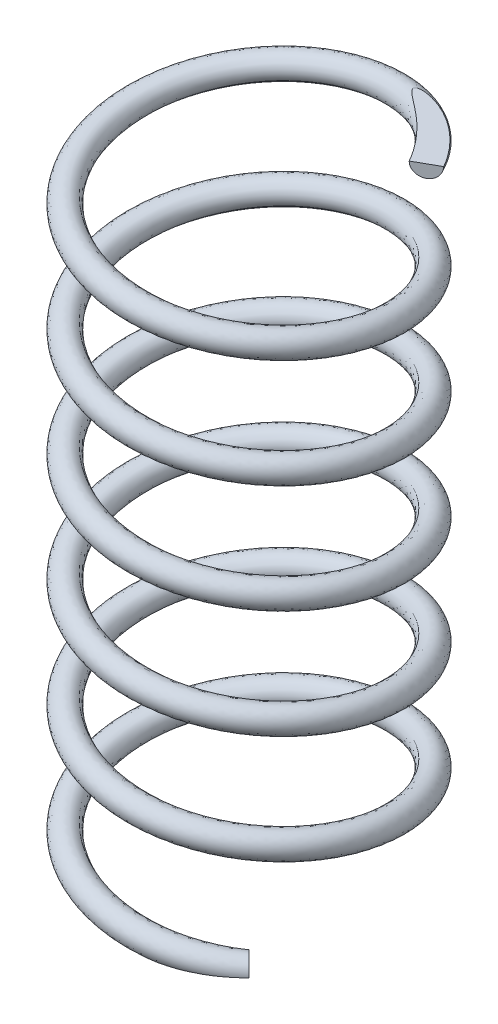
SolidWorks part; units mm, degrees
note: '?' marks a value the reader was unsure of.
material "AISI 4130 Stal normalizowana w 870C"
ref_plane "Płaszczyzna XY" through (0, 0, 0) normal (0, 0, 1) x (1, 0, 0)
ref_plane "Płaszczyzna XZ" through (0, 0, 0) normal (0, 1, 0) x (1, 0, 0)
ref_plane "Płaszczyzna YZ" through (0, 0, 0) normal (1, 0, 0) x (0, 0, -1)
sketch "Szkic1" plane through (0, 0, 0) normal (1, 0, 0) x (0, 0, -1)
  line L0 (0, -5.4086) -> (0, 11.358) construction
  circle A0 centre (-33.75, 0) radius 1.75
  point P5 (-32, 0)
  dimension "D1" = 3.5
  dimension "D2" = 32
sketch "Szkic2" plane through (0, 0, 0) normal (0, 1, 0) x (1, 0, 0)
  circle A0 centre (0, 0) radius 18
  dimension "D1" = 36
curve "Helisa/Spirala1" pitch 15 height 86.9 turns 5.7933
ref_plane "Płaszczyzna1" through (0, 0, 0) normal (0.7071, 0, -0.7071) x (-0.7071, 0, -0.7071)
sketch "Szkic3" plane through (0, 0, 0) normal (0.7071, 0, -0.7071) x (-0.7071, 0, -0.7071)
  line L0 (0, -200005.4086) -> (0, 200011.358) construction
  circle A0 centre (-18, 0) radius 1.75
  dimension "D1" = 3.5
  dimension "D2" = 18
sweep "Wyciągnięcie po ścieżce1" add profiles "Szkic3" path "Helisa/Spirala1"
sketch "Szkic4" plane through (0, 0, 0) normal (0.4909, 0, 0.8712) x (0.8712, 0, -0.4909)
  line L0 (48.3181, 86.8993) -> (-36.7385, 86.8993) construction
  line L1 (48.3181, 86.8993) -> (-36.7385, 86.8993)
  line L2 (48.3181, 86.8993) -> (48.3181, 135.4791)
  line L3 (-36.7385, 86.8993) -> (-36.7385, 135.4791)
  line L4 (48.3181, 135.4791) -> (-36.7385, 135.4791)
extrude "Wytnij-wyciągnięcie1" cut sketch "Szkic4" against normal blind 55 contours L4 L3 L1 L2
sketch "Szkic5" plane through (0, 0, 0) normal (0.7071, 0, -0.7071) x (-0.7071, 0, -0.7071)
  line L0 (-44.8219, 0) -> (45.1129, 0)
  line L1 (45.1129, 0) -> (45.1129, -13.5099)
  line L2 (45.1129, -13.5099) -> (-44.8219, -13.5099)
  line L3 (-44.8219, -13.5099) -> (-44.8219, 0)
extrude "Wytnij-wyciągnięcie2" cut sketch "Szkic5" against normal blind 55
ref_axis "Oś1" through (0, 95.0942, 0) along (0, -1, 0)?
